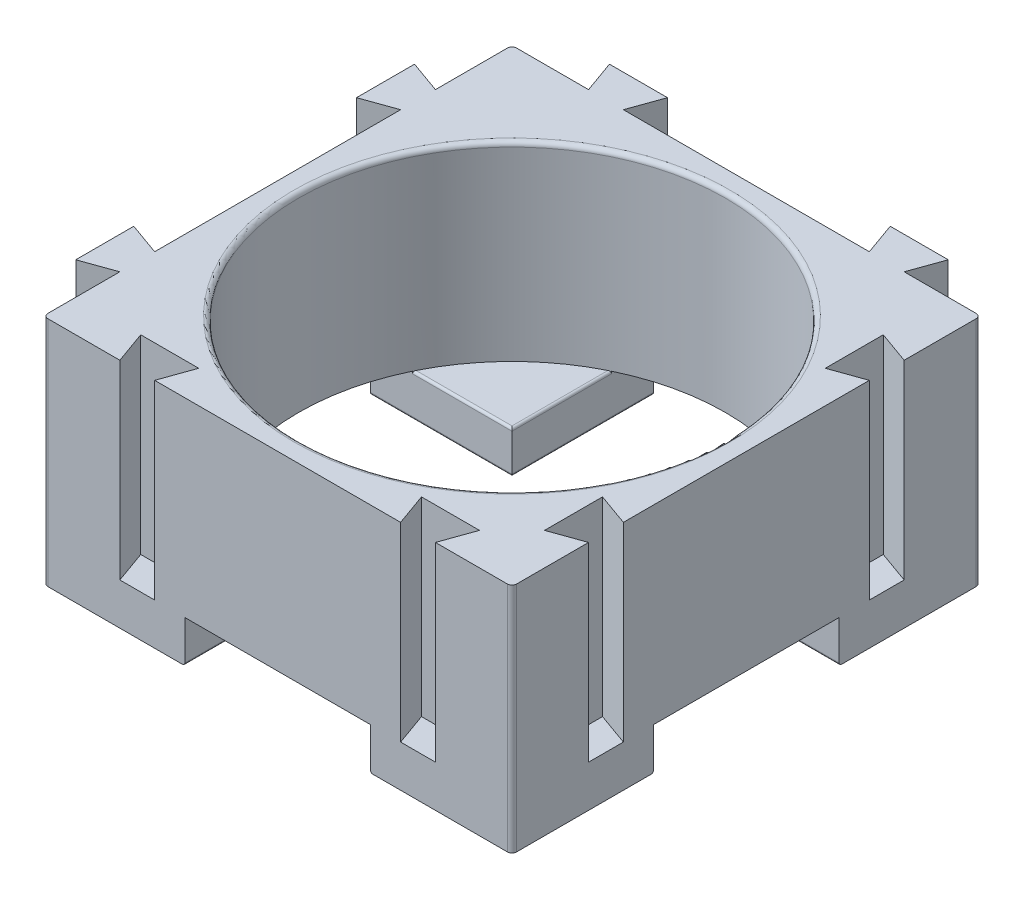
SolidWorks part; units mm, degrees
ref_plane "Ön Düzlem" through (0, 0, 0) normal (0, 0, 1) x (1, 0, 0)
ref_plane "Üst Düzlem" through (0, 0, 0) normal (0, 1, 0) x (1, 0, 0)
ref_plane "Sağ Düzlem" through (0, 0, 0) normal (1, 0, 0) x (0, 0, -1)
sketch "Çizim1" plane through (0, 0, 0) normal (0, 1, 0) x (1, 0, 0)
  line L1 (-10.1, 10.1) -> (10.1, 10.1)
  line L2 (-10.1, 10.1) -> (-10.1, -10.1)
  line L3 (-10.1, -10.1) -> (10.1, -10.1)
  line L4 (10.1, 10.1) -> (10.1, -10.1)
  line L5 (-10.1, 10.1) -> (10.1, -10.1) construction
  line L6 (-10.1, -10.1) -> (10.1, 10.1) construction
  point P0 (0, 0)
  dimension "D1" = 20.2
  dimension "D2" = 20.2
extrude "Yükseklik-Ekstrüzyon1" add sketch "Çizim1" along normal blind 10
ref_plane "Düzlem1" through (0, 1.8, 0) normal (0, 1, 0) x (1, 0, 0)
sketch "Çizim3" plane through (0, 1.8, 0) normal (0, 1, 0) x (1, 0, 0)
  circle A0 centre (0, 0) radius 9.2
extrude "Kes-Ekstrüzyon4" cut sketch "Çizim3" along normal up to surface (8.2 mm away) up to face at (0, 10, 0)
sketch "Çizim4" plane through (0, 0, 0) normal (0, 1, 0) x (1, 0, 0)
  line L10 (-4, 4) -> (-10.1, 4)
  line L11 (4, 4) -> (4, 10.1)
  line L12 (4, -4) -> (10.1, -4)
  line L13 (-4, -4) -> (-4, -10.1)
  line L14 (-4, -4) -> (4, -4)
  line L15 (4, -4) -> (4, 4)
  line L16 (4, 4) -> (-4, 4)
  line L17 (-4, 4) -> (-4, -4)
  line L18 (-10.1, -4) -> (-4, -4)
  line L19 (4, -10.1) -> (4, -4)
  line L20 (10.1, 4) -> (4, 4)
  line L21 (-4, 10.1) -> (-4, 4)
  line L22 (10.1, 10.1) -> (-10.1, 10.1) construction
  line L23 (4, 10.1) -> (-4, 10.1)
  line L24 (-10.1, 10.1) -> (-10.1, -10.1) construction
  line L25 (10.1, -10.1) -> (10.1, 10.1) construction
  line L26 (-10.1, -10.1) -> (10.1, -10.1) construction
  line L27 (-10.1, 4) -> (-10.1, -4)
  line L28 (10.1, -4) -> (10.1, 4)
  line L29 (-4, -10.1) -> (4, -10.1)
  dimension "D1" = 6.1
extrude "Kes-Ekstrüzyon5" cut sketch "Çizim4" along normal blind 1.8
sketch "Çizim5" plane through (0, 0, 0) normal (0, -1, 0) x (1, 0, 0)
  line L0 (-7.05, 7.05) -> (7.05, 7.05) construction
  line L3 (7.05, 7.05) -> (7.05, -7.05) construction
  line L6 (7.05, -7.05) -> (-7.05, -7.05) construction
  line L9 (-7.05, -7.05) -> (-7.05, 7.05) construction
  line L12 (0, 0) -> (7.05, 0) construction
  circle A0 centre (-7.05, 7.05) radius 1
  circle A1 centre (7.05, 7.05) radius 1
  circle A2 centre (7.05, -7.05) radius 1
  circle A3 centre (-7.05, -7.05) radius 1
extrude "Kes-Ekstrüzyon6" cut sketch "Çizim5" against normal blind 0.1
fillet "Radyus2" radius 0.2 1 edges at (0, 10, 9.2)
sketch "Çizim7" plane through (0, 0, 0) normal (0, 0, 1) x (1, 0, 0)
  line L2 (-9.2, 2.05) -> (-9.2, 1.8)
  line L3 (-9.2, 1.8) -> (-9, 1.8)
  line L4 (-9, 1.85) -> (-9, 1.8)
  line L5 (0, 0) -> (0, 4.4288) construction
  arc A0 (-9.2, 2.05) -> (-9, 1.85) centre (-9, 2.05) ccw
other "GrubuHizala1"
sketch "Çizim8" plane through (0, 10, 0) normal (0, 1, 0) x (1, 0, 0)
  line L4 (0, 0) -> (-11.5, 0) construction
  line L5 (-10.1, -6.8) -> (-10.1, -5.3)
  line L6 (5.3, 10.1) -> (4.8, 11.5)
  line L8 (8.7, 7.3) -> (8.7, 4.8) construction
  line L9 (8.7, 7.3) -> (10.1, 6.8) construction
  line L10 (10.1, 6.8) -> (10.1, 5.3) construction
  line L11 (10.1, 5.3) -> (8.7, 4.8) construction
  line L12 (-11.5, -7.3) -> (-10.1, -6.8)
  line L13 (-11.5, -7.3) -> (-11.5, -4.8)
  line L14 (-11.5, 7.3) -> (-11.5, 4.8)
  line L15 (-10.1, -5.3) -> (-11.5, -4.8)
  line L16 (6.8, 10.1) -> (5.3, 10.1)
  line L17 (7.3, 11.5) -> (6.8, 10.1)
  line L18 (7.3, 11.5) -> (4.8, 11.5)
  line L19 (-7.3, 11.5) -> (-4.8, 11.5)
  line L20 (-5.3, 10.1) -> (-4.8, 11.5)
  line L21 (-7.3, 11.5) -> (-6.8, 10.1)
  line L22 (-6.8, 10.1) -> (-5.3, 10.1)
  line L23 (10.1, -5.3) -> (8.7, -4.8) construction
  line L24 (-11.5, 7.3) -> (-10.1, 6.8)
  line L25 (-10.1, 5.3) -> (-11.5, 4.8)
  line L26 (8.7, -7.3) -> (8.7, -4.8) construction
  line L27 (8.7, -7.3) -> (10.1, -6.8) construction
  line L28 (10.1, -6.8) -> (10.1, -5.3) construction
  line L29 (-6.8, -10.1) -> (-5.3, -10.1) construction
  line L31 (-10.1, 6.8) -> (-10.1, 5.3)
  line L33 (-7.3, -8.7) -> (-4.8, -8.7) construction
  line L34 (-7.3, -8.7) -> (-6.8, -10.1) construction
  line L35 (-5.3, -10.1) -> (-4.8, -8.7) construction
  line L36 (7.3, -8.7) -> (4.8, -8.7) construction
  line L37 (7.3, -8.7) -> (6.8, -10.1) construction
  line L38 (5.3, -10.1) -> (4.8, -8.7) construction
  line L39 (6.8, -10.1) -> (5.3, -10.1) construction
  point P23 (0, 0)
  dimension "D1" = 2
  dimension "D2" = 2
extrude "Yükseklik-Ekstrüzyon3" add sketch "Çizim8" against normal blind 8.2
sketch "Çizim9" plane through (0, 10, 0) normal (0, 1, 0) x (1, 0, 0)
  line L16 (8.7, -7.3) -> (12.2, -6.05)
  line L17 (8.7, -7.3) -> (8.7, -4.8)
  line L18 (12.2, -6.05) -> (8.7, -4.8)
  line L20 (8.7, 7.3) -> (8.7, 4.8)
  line L21 (8.7, 7.3) -> (12.2, 6.05)
  line L23 (12.2, 6.05) -> (8.7, 4.8)
  line L24 (-7.3, -8.7) -> (-4.8, -8.7)
  line L25 (-7.3, -8.7) -> (-6.05, -12.2)
  line L26 (-6.05, -12.2) -> (-4.8, -8.7)
  line L28 (7.3, -8.7) -> (4.8, -8.7)
  line L30 (6.05, -12.2) -> (4.8, -8.7)
  line L31 (7.3, -8.7) -> (6.05, -12.2)
extrude "Kes-Ekstrüzyon7" cut sketch "Çizim9" against normal blind 8.2
fillet "Radyus3" radius 0.2 4 edges at (-10.1, 5, -10.1) (10.1, 5, -10.1) (10.1, 5, 10.1) (-10.1, 5, 10.1)
fillet "Radyus5" radius 0.1 16 edges at (-4, 1.8, -6.1425) (-6.1425, 1.8, -4) (-7.05, 0, 4) (-4, 0, 7.05) (-4, 1.8, 6.1425) (-6.1425, 1.8, 4) (4, 0, 7.05) (7.05, 0, 4) (6.1425, 1.8, 4) (4, 1.8, 6.1425) (7.05, 0, -4) (6.1425, 1.8, -4) (4, 0, -7.05) (4, 1.8, -6.1425) (-4, 0, -7.05) (-7.05, 0, -4)
